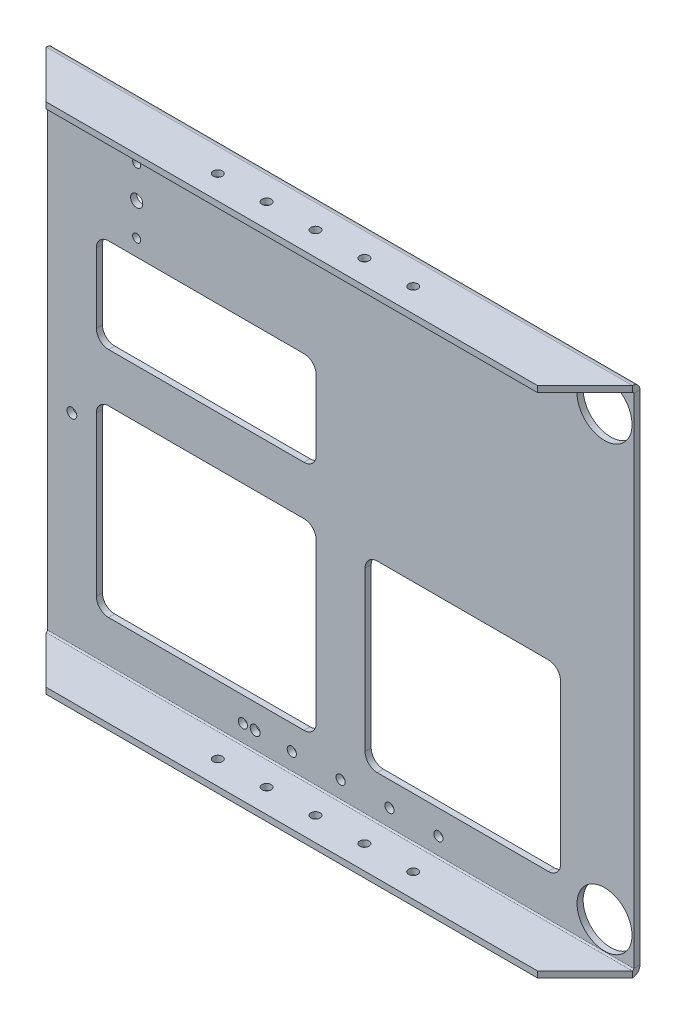
SolidWorks part; units mm, degrees
note: The reader was unsure of these and kept them because the rebuilt part matched: flange length of "Edge-Flange1", "Edge-Flange2".
ref_plane "FRONT" through (0, 0, 0) normal (0, 0, 1) x (1, 0, 0)
ref_plane "TOP" through (0, 0, 0) normal (0, 1, 0) x (1, 0, 0)
ref_plane "RIGHT" through (0, 0, 0) normal (1, 0, 0) x (0, 0, -1)
sketch "Sketch1" plane through (0, 0, 0) normal (0, 0, 1) x (1, 0, 0)
  line L0 (0, 133.35) -> (304.8, 133.35) construction
  line L1 (0, 0) -> (304.8, 0)
  line L2 (0, 0) -> (0, 266.7)
  line L3 (0, 266.7) -> (304.8, 266.7)
  line L4 (304.8, 0) -> (304.8, 266.7)
  line L5 (152.4, 266.7) -> (152.4, 0) construction
  line L6 (171.45, 120.65) -> (260.35, 120.65)
  line L7 (165.1, 114.3) -> (165.1, 31.75)
  line L8 (171.45, 25.4) -> (260.35, 25.4)
  line L9 (266.7, 114.3) -> (266.7, 31.75)
  line L10 (31.75, 120.65) -> (133.35, 120.65)
  line L11 (25.4, 114.3) -> (25.4, 31.75)
  line L12 (31.75, 25.4) -> (133.35, 25.4)
  line L13 (139.7, 114.3) -> (139.7, 31.75)
  line L14 (46.355, 237.1878) -> (46.355, 203.5022) construction
  line L15 (31.75, 194.945) -> (133.35, 194.945)
  line L16 (25.4, 188.595) -> (25.4, 152.4)
  line L17 (31.75, 146.05) -> (133.35, 146.05)
  line L18 (139.7, 188.595) -> (139.7, 152.4)
  line L19 (304.8, 12.7) -> (0, 12.7) construction
  line L20 (152.4, 12.7) -> (177.8, 12.7) construction
  line L21 (152.4, 12.7) -> (127, 12.7) construction
  line L22 (152.4, 254) -> (127, 254) construction
  line L23 (152.4, 254) -> (177.8, 254) construction
  circle A0 centre (289.56, 18.415) radius 14.2875
  circle A1 centre (289.56, 248.285) radius 14.2875
  circle A2 centre (46.355, 220.345) radius 3.175
  arc A3 (171.45, 120.65) -> (165.1, 114.3) centre (171.45, 114.3) ccw
  arc A4 (165.1, 31.75) -> (171.45, 25.4) centre (171.45, 31.75) ccw
  arc A5 (266.7, 31.75) -> (260.35, 25.4) centre (260.35, 31.75) cw
  arc A6 (266.7, 114.3) -> (260.35, 120.65) centre (260.35, 114.3) ccw
  arc A7 (31.75, 120.65) -> (25.4, 114.3) centre (31.75, 114.3) ccw
  arc A8 (25.4, 31.75) -> (31.75, 25.4) centre (31.75, 31.75) ccw
  arc A9 (139.7, 31.75) -> (133.35, 25.4) centre (133.35, 31.75) cw
  arc A10 (139.7, 114.3) -> (133.35, 120.65) centre (133.35, 114.3) ccw
  circle A11 centre (46.355, 220.345) radius 16.8428 construction
  circle A12 centre (46.355, 237.1878) radius 2.0955
  circle A13 centre (46.355, 203.5022) radius 2.0955
  arc A14 (31.75, 194.945) -> (25.4, 188.595) centre (31.75, 188.595) ccw
  arc A15 (25.4, 152.4) -> (31.75, 146.05) centre (31.75, 152.4) ccw
  arc A16 (139.7, 152.4) -> (133.35, 146.05) centre (133.35, 152.4) cw
  arc A17 (139.7, 188.595) -> (133.35, 194.945) centre (133.35, 188.595) ccw
  circle A18 centre (152.4, 12.7) radius 2.3876
  circle A19 centre (177.8, 12.7) radius 2.3876
  circle A20 centre (203.2, 12.7) radius 2.3876
  circle A21 centre (127, 12.7) radius 2.3876
  circle A22 centre (101.6, 12.7) radius 2.3876
  circle A23 centre (101.6, 254) radius 2.3876
  circle A24 centre (127, 254) radius 2.3876
  circle A25 centre (203.2, 254) radius 2.3876
  circle A26 centre (177.8, 254) radius 2.3876
  circle A27 centre (152.4, 254) radius 2.3876
  circle A28 centre (107.95, 12.7) radius 2.5527
  circle A29 centre (12.7, 107.95) radius 2.5527
  dimension "D3" = 28.575
  dimension "D6" = 6.35
  dimension "D9" = 6.35
  dimension "D10" = 6.35
  dimension "D19" = 6.35
  dimension "D20" = 6.35
  dimension "D21" = 33.6857
  dimension "D22" = 4.191
  dimension "D23" = 6.35
  dimension "D24" = 6.35
  dimension "D30" = 4.7752
  dimension "D33" = 5.1054
  dimension "D35" = 12.7
  dimension "D38" = 12.7
  dimension "D39" = 5.1054
  dimension "D1" = 266.7
  dimension "D2" = 304.8
  dimension "D4" = 15.24
  dimension "D5" = 18.415
  dimension "D7" = 46.355
  dimension "D8" = 46.355
  dimension "D11" = 38.1
  dimension "D12" = 25.4
  dimension "D13" = 12.7
  dimension "D14" = 12.7
  dimension "D15" = 25.4
  dimension "D16" = 25.4
  dimension "D17" = 12.7
  dimension "D18" = 12.7
  dimension "D25" = 12.7
  dimension "D26" = 25.4
  dimension "D27" = 12.7
  dimension "D28" = 25.4
  dimension "D29" = 12.7
  dimension "D34" = 107.95
  dimension "D32" = 25.4
  dimension "D37" = 25.4
  dimension "D40" = 107.95
  dimension "D41" = 12.7
  dimension "D31" = 3
  dimension "D36" = 3
base flange "Base-Flange1" sketch "Sketch1" thickness 3.175 reverse thickness direction no parameters "D1"=0.7366
edge flange "Edge-Flange1" sketch "Sketch8" flange angle 90 flange length 28.575 flange position material inside bend radius 0.7366 thickness 3.175 relief rectangular parameters "D6"=10
sketch "Sketch8" plane through (0, 266.7, 0) normal (0, -1, 0) x (1, 0, 0)
  line L1 (304.8, 0) -> (0, 0) construction
  line L2 (0, 0) -> (0, 25.4)
  line L3 (0, 25.4) -> (304.8, 25.4)
  line L4 (304.8, 25.4) -> (304.8, 0)
  line L5 (304.8, 0) -> (0, 0)
bend "EdgeBend1" bend radius 0.7366 bend angle 90 parameters "D5"=1
edge flange "Edge-Flange2" sketch "Sketch11" flange angle 90 flange length 28.575 flange position material inside bend radius 0.7366 thickness 3.175 relief rectangular parameters "D6"=10
sketch "Sketch11" plane through (0, 0, 0) normal (0, 1, 0) x (-1, 0, 0)
  line L1 (0, 0) -> (-304.8, 0) construction
  line L2 (-304.8, 0) -> (-304.8, 25.4)
  line L3 (-304.8, 25.4) -> (0, 25.4)
  line L4 (0, 25.4) -> (0, 0)
  line L5 (0, 0) -> (-304.8, 0)
bend "EdgeBend2" bend radius 0.7366 bend angle 90 parameters "D5"=2
sketch "Sketch12" plane through (0, 0, 0) normal (0, -1, 0) x (-1, 0, 0)
  line L0 (-304.8, -0.7366) -> (-280.1366, -25.4)
  line L1 (0, -25.4) -> (-304.8, -25.4) construction
  line L2 (-280.1366, -25.4) -> (-304.8, -25.4)
  line L3 (-304.8, -25.4) -> (-304.8, -0.7366)
  line L4 (0, -0.7366) -> (-304.8, -0.7366) construction
  dimension "D1" = 45
extrude "Cut-Extrude1" cut sketch "Sketch12" against normal through all normal cut yes
sketch "Sketch14" plane through (0, 0, 0) normal (0, -1, 0) x (1, 0, 0)
  line L0 (0, 0.7366) -> (24.6634, 25.4)
  line L1 (0, 25.4) -> (280.1366, 25.4) construction
  line L2 (24.6634, 25.4) -> (0, 25.4)
  line L3 (0, 25.4) -> (0, 0.7366)
  line L4 (0, 0.7366) -> (304.8, 0.7366) construction
  dimension "D1" = 45
extrude "Cut-Extrude2" cut sketch "Sketch14" against normal through all normal cut yes
sketch "Sketch15" plane through (0, 0, 0) normal (0, -1, 0) x (1, 0, 0)
  line L0 (152.4, 0.7366) -> (152.4, 25.4) construction
  line L1 (0, 0.7366) -> (304.8, 0.7366) construction
  line L2 (24.6634, 25.4) -> (280.1366, 25.4) construction
  line L3 (152.4, 13.0683) -> (177.8, 13.0683) construction
  line L4 (152.4, 13.0683) -> (127, 13.0683) construction
  circle A0 centre (152.4, 13.0683) radius 2.3876
  circle A1 centre (177.8, 13.0683) radius 2.3876
  circle A2 centre (203.2, 13.0683) radius 2.3876
  circle A3 centre (127, 13.0683) radius 2.3876
  circle A4 centre (101.6, 13.0683) radius 2.3876
  dimension "D1" = 4.7752
  dimension "D4" = 12.3317
  dimension "D7" = 12.3317
  dimension "D3" = 25.4
  dimension "D6" = 25.4
  dimension "D2" = 3
  dimension "D5" = 3
extrude "Cut-Extrude3" cut sketch "Sketch15" against normal through all normal cut yes
sketch "Bend-Lines1" [suppressed] plane through (0, 0, 0) normal (0, 1, 0) x (1, 0, 0)
sketch "Bounding-Box1" [suppressed] plane through (0, 0, 0) normal (0, 1, 0) x (1, 0, 0)
sheet metal parameters "Sheet-Metal5" thickness 3.175 parameters "D1"=0.7366
flat pattern "Flat-Pattern5" [suppressed]
sketch "Bend-Lines2" plane through (0, 0, 0) normal (0, 1, 0) x (1, 0, 0)
sketch3d "Bounding-Box2" [suppressed]
  line L0 (0, 0, 0) -> (-304.8, 0, 0) construction
  line L1 (0, 266.7, 0) -> (-304.8, 266.7, 0) construction
  line L2 (0, 0, 0) -> (0, 266.7, 0) construction
  line L3 (-304.8, 0, 0) -> (-304.8, 266.7, 0) construction
sheet metal parameters "Sheet-Metal6" thickness 3.175 parameters "D1"=0.7366
flat pattern "Flat-Pattern5"
sketch "Bend-Lines2" plane through (0, 0, 0) normal (0, 0, 1) x (1, 0, 0)
  line L0 (304.8, 264.1898) -> (0, 264.1898) construction
  line L1 (304.8, 264.1898) -> (0, 264.1898) construction
sketch3d "Bounding-Box2" [suppressed]
  line L0 (0, 0, 0) -> (304.8, 0, 0) construction
  line L1 (0, 290.2547, 0) -> (304.8, 290.2547, 0) construction
  line L2 (0, 0, 0) -> (0, 290.2547, 0) construction
  line L3 (304.8, 0, 0) -> (304.8, 290.2547, 0) construction
bend of the flat pattern "Flatten-<EdgeBend1>1"
sheet metal parameters "Sheet-Metal7" thickness 3.175 parameters "D1"=0.7366
flat pattern "Flat-Pattern5"
sketch "Bend-Lines2" plane through (0, 0, 0) normal (0, 0, 1) x (1, 0, 0)
  line L0 (304.8, 264.1898) -> (0, 264.1898) construction
  line L1 (304.8, 264.1898) -> (0, 264.1898) construction
  line L2 (0, 2.5102) -> (304.8, 2.5102) construction
  line L3 (0, 2.5102) -> (304.8, 2.5102) construction
sketch3d "Bounding-Box2" [suppressed]
  line L0 (304.8, 290.2547, 0) -> (304.8, -23.5547, 0) construction
  line L1 (0, 290.2547, 0) -> (0, -23.5547, 0) construction
  line L2 (304.8, 290.2547, 0) -> (0, 290.2547, 0) construction
  line L3 (304.8, -23.5547, 0) -> (0, -23.5547, 0) construction
bend of the flat pattern "Flatten-<EdgeBend1>1"
bend of the flat pattern "Flatten-<EdgeBend2>1"
sheet metal parameters "Sheet-Metal8" thickness 3.175 parameters "D1"=0.7366
flat pattern "Flat-Pattern5"
sketch "Bend-Lines2" plane through (0, 0, 0) normal (0, 0, 1) x (1, 0, 0)
  line L0 (304.8, 264.1898) -> (0, 264.1898) construction
  line L1 (304.8, 264.1898) -> (0, 264.1898) construction
  line L2 (0, 2.5102) -> (304.8, 2.5102) construction
  line L3 (0, 2.5102) -> (304.8, 2.5102) construction
sketch3d "Bounding-Box2" [suppressed]
  line L0 (304.8, 290.2547, 0) -> (304.8, -23.5547, 0) construction
  line L1 (0, 290.2547, 0) -> (0, -23.5547, 0) construction
  line L2 (304.8, 290.2547, 0) -> (0, 290.2547, 0) construction
  line L3 (304.8, -23.5547, 0) -> (0, -23.5547, 0) construction
bend of the flat pattern "Flatten-<EdgeBend1>1"
bend of the flat pattern "Flatten-<EdgeBend2>1"
sheet metal parameters "Sheet-Metal9" thickness 3.175 parameters "D1"=0.7366
flat pattern "Flat-Pattern5"
sketch "Bend-Lines2" plane through (0, 0, 0) normal (0, 0, 1) x (1, 0, 0)
  line L0 (304.8, 264.1898) -> (0, 264.1898) construction
  line L1 (304.8, 264.1898) -> (0, 264.1898) construction
  line L2 (0, 2.5102) -> (304.8, 2.5102) construction
  line L3 (0, 2.5102) -> (304.8, 2.5102) construction
sketch3d "Bounding-Box2" [suppressed]
  line L0 (304.8, 290.2547, 0) -> (304.8, -23.5547, 0) construction
  line L1 (0, 290.2547, 0) -> (0, -23.5547, 0) construction
  line L2 (304.8, 290.2547, 0) -> (0, 290.2547, 0) construction
  line L3 (304.8, -23.5547, 0) -> (0, -23.5547, 0) construction
bend of the flat pattern "Flatten-<EdgeBend1>1"
bend of the flat pattern "Flatten-<EdgeBend2>1"
sheet metal parameters "Sheet-Metal10" thickness 3.175 parameters "D1"=0.7366
flat pattern "Flat-Pattern5"
sketch "Bend-Lines2" plane through (0, 0, 0) normal (0, 0, 1) x (1, 0, 0)
  line L0 (304.8, 264.1898) -> (0, 264.1898) construction
  line L1 (304.8, 264.1898) -> (0, 264.1898) construction
  line L2 (0, 2.5102) -> (304.8, 2.5102) construction
  line L3 (0, 2.5102) -> (304.8, 2.5102) construction
sketch3d "Bounding-Box2" [suppressed]
  line L0 (304.8, 290.2547, 0) -> (304.8, -23.5547, 0) construction
  line L1 (0, 290.2547, 0) -> (0, -23.5547, 0) construction
  line L2 (304.8, 290.2547, 0) -> (0, 290.2547, 0) construction
  line L3 (304.8, -23.5547, 0) -> (0, -23.5547, 0) construction
bend of the flat pattern "Flatten-<EdgeBend1>1"
bend of the flat pattern "Flatten-<EdgeBend2>1"
